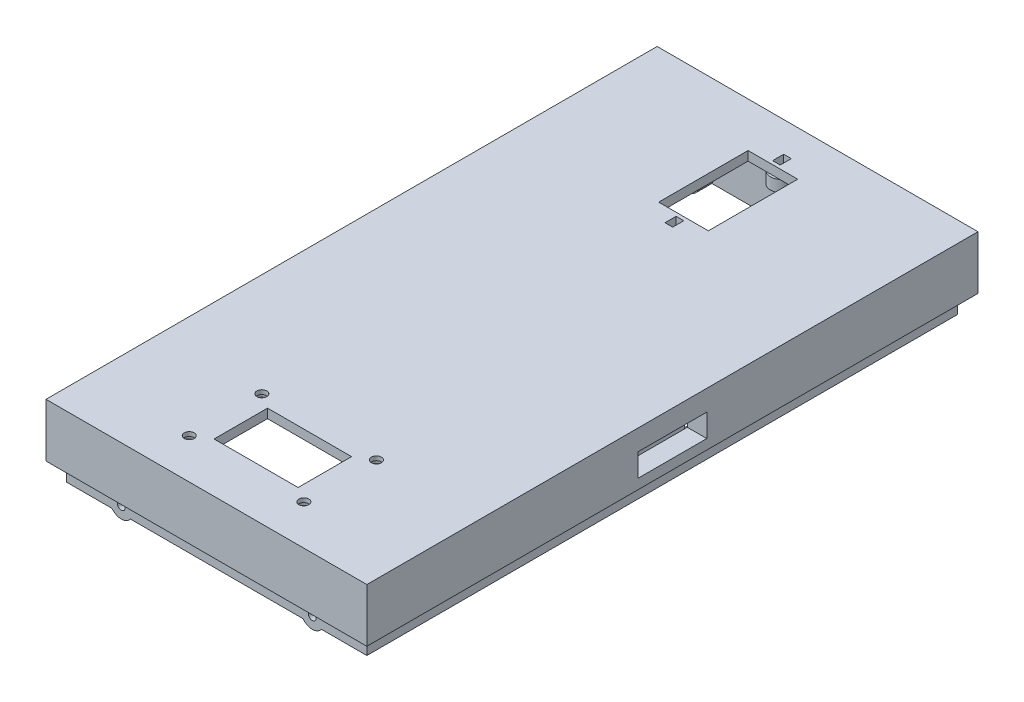
SolidWorks part; units mm, degrees
ref_plane "Front Plane" through (0, 0, 0) normal (0, 0, 1) x (1, 0, 0)
ref_plane "Top Plane" through (0, 0, 0) normal (0, 1, 0) x (1, 0, 0)
ref_plane "Right Plane" through (0, 0, 0) normal (1, 0, 0) x (0, 0, -1)
sketch "Sketch1" plane through (0, 0, 0) normal (0, 0, 1) x (1, 0, 0)
  line L1 (-42, 36) -> (42, 36)
  line L2 (-42, 36) -> (-42, 50)
  line L3 (-42, 50) -> (42, 50)
  line L4 (42, 36) -> (42, 50)
extrude "Boss-Extrude1" add sketch "Sketch1" along normal blind 160 from offset 80 offset against normal yes
sketch "Sketch2" plane through (0, 0, 0) normal (0, 0, 1) x (1, 0, 0)
  line L1 (-39.3, 31.2) -> (39.3, 31.2)
  line L2 (-39.3, 31.2) -> (-39.3, 36.5)
  line L3 (-39.3, 36.5) -> (39.3, 36.5)
  line L4 (39.3, 31.2) -> (39.3, 36.5)
extrude "Boss-Extrude2" add sketch "Sketch2" along normal blind 154.6 from offset 77.3 offset against normal yes
sketch "Sketch3" plane through (0, 0, 0) normal (0, 0, 1) x (1, 0, 0)
  line L1 (-36.9, 30.2) -> (36.9, 30.2)
  line L2 (-36.9, 30.2) -> (-36.9, 47.6)
  line L3 (-36.9, 47.6) -> (36.9, 47.6)
  line L4 (36.9, 30.2) -> (36.9, 47.6)
extrude "Boss-Extrude3" add sketch "Sketch3" along normal blind 149.8 from offset 74.9 separate body offset against normal yes
combine bodies "Combine1" operation type subtract main body 102 bodies to subtract 103
sketch "Sketch4" plane through (0, 0, 0) normal (0, 0, 1) x (1, 0, 0)
  circle A0 centre (-25, 33) radius 3
extrude "Boss-Extrude4" add sketch "Sketch4" along normal blind 6.3 from offset 77.3 offset against normal yes
sketch "Sketch5" plane through (0, 0, 0) normal (0, 0, 1) x (1, 0, 0)
  circle A0 centre (-25, 33) radius 1
extrude "Boss-Extrude5" add sketch "Sketch5" along normal blind 8 from offset 78 separate body offset against normal yes
combine bodies "Combine2" operation type subtract main body 105 bodies to subtract 106
sketch "Sketch6" plane through (0, 0, 0) normal (0, 0, 1) x (1, 0, 0)
  circle A0 centre (25, 33) radius 3
extrude "Boss-Extrude6" add sketch "Sketch6" along normal blind 6.3 from offset 77.3 offset against normal yes
sketch "Sketch7" plane through (0, 0, 0) normal (0, 0, 1) x (1, 0, 0)
  circle A0 centre (25, 33) radius 1
extrude "Boss-Extrude7" add sketch "Sketch7" along normal blind 8 from offset 78 separate body offset against normal yes
combine bodies "Combine3" operation type subtract main body 108 bodies to subtract 109
sketch "Sketch8" plane through (0, 0, 0) normal (0, 0, 1) x (1, 0, 0)
  circle A0 centre (-25, 33) radius 3
extrude "Boss-Extrude8" add sketch "Sketch8" along normal blind 6.3 from offset 71
sketch "Sketch9" plane through (0, 0, 0) normal (0, 0, 1) x (1, 0, 0)
  circle A0 centre (-25, 33) radius 1
extrude "Boss-Extrude9" add sketch "Sketch9" along normal blind 8 from offset 70 separate body
combine bodies "Combine4" operation type subtract main body 111 bodies to subtract 112
sketch "Sketch10" plane through (0, 0, 0) normal (0, 0, 1) x (1, 0, 0)
  circle A0 centre (25, 33) radius 3
extrude "Boss-Extrude10" add sketch "Sketch10" along normal blind 6.3 from offset 71
sketch "Sketch11" plane through (0, 0, 0) normal (0, 0, 1) x (1, 0, 0)
  circle A0 centre (25, 33) radius 1
extrude "Boss-Extrude11" add sketch "Sketch11" along normal blind 8 from offset 70 separate body
combine bodies "Combine5" operation type subtract main body 114 bodies to subtract 115
sketch "Sketch12" plane through (0, 0, 0) normal (0, 0, 1) x (1, 0, 0)
  line L1 (-11, 46.6) -> (11, 46.6)
  line L2 (-11, 46.6) -> (-11, 51)
  line L3 (-11, 51) -> (11, 51)
  line L4 (11, 46.6) -> (11, 51)
extrude "Boss-Extrude12" add sketch "Sketch12" along normal blind 14 from offset 53 separate body
combine bodies "Combine6" operation type subtract main body 116 bodies to subtract 117
sketch "Sketch13" plane through (0, 0, 0) normal (0, 1, 0) x (1, 0, 0)
  circle A0 centre (-15, -50.5) radius 1.3
extrude "Boss-Extrude13" add sketch "Sketch13" along normal blind 4.4 from offset 46.6 separate body
combine bodies "Combine7" operation type subtract main body 118 bodies to subtract 119
sketch "Sketch14" plane through (0, 0, 0) normal (0, 1, 0) x (1, 0, 0)
  circle A0 centre (-15, -50.5) radius 2.3
extrude "Boss-Extrude14" add sketch "Sketch14" along normal blind 1.8 from offset 47.1 separate body
combine bodies "Combine8" operation type subtract main body 120 bodies to subtract 121
sketch "Sketch15" plane through (0, 0, 0) normal (0, 1, 0) x (1, 0, 0)
  circle A0 centre (-15, -69.5) radius 1.3
extrude "Boss-Extrude15" add sketch "Sketch15" along normal blind 4.4 from offset 46.6 separate body
combine bodies "Combine9" operation type subtract main body 122 bodies to subtract 123
sketch "Sketch16" plane through (0, 0, 0) normal (0, 1, 0) x (1, 0, 0)
  circle A0 centre (-15, -69.5) radius 2.3
extrude "Boss-Extrude16" add sketch "Sketch16" along normal blind 1.8 from offset 47.1 separate body
combine bodies "Combine10" operation type subtract main body 124 bodies to subtract 125
sketch "Sketch17" plane through (0, 0, 0) normal (0, 1, 0) x (1, 0, 0)
  circle A0 centre (15, -50.5) radius 1.3
extrude "Boss-Extrude17" add sketch "Sketch17" along normal blind 4.4 from offset 46.6 separate body
combine bodies "Combine11" operation type subtract main body 126 bodies to subtract 127
sketch "Sketch18" plane through (0, 0, 0) normal (0, 1, 0) x (1, 0, 0)
  circle A0 centre (15, -50.5) radius 2.3
extrude "Boss-Extrude18" add sketch "Sketch18" along normal blind 1.8 from offset 47.1 separate body
combine bodies "Combine12" operation type subtract main body 128 bodies to subtract 129
sketch "Sketch19" plane through (0, 0, 0) normal (0, 1, 0) x (1, 0, 0)
  circle A0 centre (15, -69.5) radius 1.3
extrude "Boss-Extrude19" add sketch "Sketch19" along normal blind 4.4 from offset 46.6 separate body
combine bodies "Combine13" operation type subtract main body 130 bodies to subtract 131
sketch "Sketch20" plane through (0, 0, 0) normal (0, 1, 0) x (1, 0, 0)
  circle A0 centre (15, -69.5) radius 2.3
extrude "Boss-Extrude20" add sketch "Sketch20" along normal blind 1.8 from offset 47.1 separate body
combine bodies "Combine14" operation type subtract main body 132 bodies to subtract 133
sketch "Sketch21" plane through (0, 0, 0) normal (0, 0, 1) x (1, 0, 0)
  line L1 (-6.5, 46.6) -> (6.5, 46.6)
  line L2 (-6.5, 46.6) -> (-6.5, 51)
  line L3 (-6.5, 51) -> (6.5, 51)
  line L4 (6.5, 46.6) -> (6.5, 51)
extrude "Boss-Extrude21" add sketch "Sketch21" along normal blind 23.4 from offset 68.3 separate body offset against normal yes
combine bodies "Combine15" operation type subtract main body 134 bodies to subtract 135
sketch "Sketch22" plane through (0, 0, 0) normal (0, 1, 0) x (1, 0, 0)
  circle A0 centre (0, 70.675) radius 3
extrude "Boss-Extrude22" add sketch "Sketch22" along normal blind 3 from offset 44.6
sketch "Sketch23" plane through (0, 0, 0) normal (0, 0, 1) x (1, 0, 0)
  line L1 (-1, 43.6) -> (1, 43.6)
  line L2 (-1, 43.6) -> (-1, 51)
  line L3 (-1, 51) -> (1, 51)
  line L4 (1, 43.6) -> (1, 51)
extrude "Boss-Extrude23" add sketch "Sketch23" along normal blind 2.9 from offset 72.125 separate body offset against normal yes
combine bodies "Combine16" operation type subtract main body 137 bodies to subtract 138
sketch "Sketch24" plane through (0, 0, 0) normal (0, 1, 0) x (1, 0, 0)
  circle A0 centre (0, 42.525) radius 3
extrude "Boss-Extrude24" add sketch "Sketch24" along normal blind 3 from offset 44.6
sketch "Sketch25" plane through (0, 0, 0) normal (0, 0, 1) x (1, 0, 0)
  line L1 (-1, 43.6) -> (1, 43.6)
  line L2 (-1, 43.6) -> (-1, 51)
  line L3 (-1, 51) -> (1, 51)
  line L4 (1, 43.6) -> (1, 51)
extrude "Boss-Extrude25" add sketch "Sketch25" along normal blind 2.9 from offset 43.975 separate body offset against normal yes
combine bodies "Combine17" operation type subtract main body 140 bodies to subtract 141
sketch "Sketch26" plane through (0, 0, 0) normal (0, 0, 1) x (1, 0, 0)
  line L1 (-43, 38.6) -> (-36, 38.6)
  line L2 (-43, 38.6) -> (-43, 44.6)
  line L3 (-43, 44.6) -> (-36, 44.6)
  line L4 (-36, 38.6) -> (-36, 44.6)
extrude "Boss-Extrude26" add sketch "Sketch26" along normal blind 18 from offset 9 separate body offset against normal yes
combine bodies "Combine18" operation type subtract main body 142 bodies to subtract 143
sketch "Sketch27" plane through (0, 0, 0) normal (0, 0, 1) x (1, 0, 0)
  line L1 (-36.9, 34.4) -> (-33.6, 34.4)
  line L2 (-36.9, 34.4) -> (-36.9, 35.6)
  line L3 (-36.9, 35.6) -> (-33.6, 35.6)
  line L4 (-33.6, 34.4) -> (-33.6, 35.6)
extrude "Boss-Extrude27" add sketch "Sketch27" along normal blind 27 from offset 13.5 offset against normal yes
sketch "Sketch28" plane through (0, 0, 0) normal (0, 0, 1) x (1, 0, 0)
  line L1 (-34.2, 34.4) -> (-33, 34.4)
  line L2 (-34.2, 34.4) -> (-34.2, 38)
  line L3 (-34.2, 38) -> (-33, 38)
  line L4 (-33, 34.4) -> (-33, 38)
extrude "Boss-Extrude28" add sketch "Sketch28" along normal blind 22 from offset 11 offset against normal yes
sketch "Sketch29" plane through (0, 0, 0) normal (0, 0, 1) x (1, 0, 0)
  line L1 (36, 38.6) -> (43, 38.6)
  line L2 (36, 38.6) -> (36, 44.6)
  line L3 (36, 44.6) -> (43, 44.6)
  line L4 (43, 38.6) -> (43, 44.6)
extrude "Boss-Extrude29" add sketch "Sketch29" along normal blind 18 from offset 9 separate body offset against normal yes
combine bodies "Combine19" operation type subtract main body 146 bodies to subtract 147
sketch "Sketch30" plane through (0, 0, 0) normal (0, 0, 1) x (1, 0, 0)
  line L1 (33.6, 34.4) -> (36.9, 34.4)
  line L2 (33.6, 34.4) -> (33.6, 35.6)
  line L3 (33.6, 35.6) -> (36.9, 35.6)
  line L4 (36.9, 34.4) -> (36.9, 35.6)
extrude "Boss-Extrude30" add sketch "Sketch30" along normal blind 27 from offset 13.5 offset against normal yes
sketch "Sketch31" plane through (0, 0, 0) normal (0, 0, 1) x (1, 0, 0)
  line L1 (33, 34.4) -> (34.2, 34.4)
  line L2 (33, 34.4) -> (33, 38)
  line L3 (33, 38) -> (34.2, 38)
  line L4 (34.2, 34.4) -> (34.2, 38)
extrude "Boss-Extrude31" add sketch "Sketch31" along normal blind 22 from offset 11 offset against normal yes
sketch "Sketch32" plane through (0, 0, 0) normal (0, 0, 1) x (1, 0, 0)
  line L1 (-9.8, 45.1) -> (-8.6, 45.1)
  line L2 (-9.8, 45.1) -> (-9.8, 47.6)
  line L3 (-9.8, 47.6) -> (-8.6, 47.6)
  line L4 (-8.6, 45.1) -> (-8.6, 47.6)
extrude "Boss-Extrude32" add sketch "Sketch32" along normal blind 22.4 from offset 3.6
sketch "Sketch33" plane through (0, 0, 0) normal (0, 0, 1) x (1, 0, 0)
  line L1 (8.6, 45.1) -> (9.8, 45.1)
  line L2 (8.6, 45.1) -> (8.6, 47.6)
  line L3 (8.6, 47.6) -> (9.8, 47.6)
  line L4 (9.8, 45.1) -> (9.8, 47.6)
extrude "Boss-Extrude33" add sketch "Sketch33" along normal blind 22.4 from offset 3.6
sketch "Sketch34" plane through (0, 0, 0) normal (0, 0, 1) x (1, 0, 0)
  line L1 (-9.8, 45.1) -> (9.8, 45.1)
  line L2 (-9.8, 45.1) -> (-9.8, 47.6)
  line L3 (-9.8, 47.6) -> (9.8, 47.6)
  line L4 (9.8, 45.1) -> (9.8, 47.6)
extrude "Boss-Extrude34" add sketch "Sketch34" along normal blind 1.2 from offset 2.4
sketch "Sketch35" plane through (0, 0, 0) normal (0, 0, 1) x (1, 0, 0)
  line L1 (-9.8, 45.1) -> (9.8, 45.1)
  line L2 (-9.8, 45.1) -> (-9.8, 47.6)
  line L3 (-9.8, 47.6) -> (9.8, 47.6)
  line L4 (9.8, 45.1) -> (9.8, 47.6)
extrude "Boss-Extrude35" add sketch "Sketch35" along normal blind 1.2 from offset 26
sketch "Sketch36" plane through (0, 0, 0) normal (0, 0, 1) x (1, 0, 0)
  line L1 (14.9, 45.1) -> (16.1, 45.1)
  line L2 (14.9, 45.1) -> (14.9, 47.6)
  line L3 (14.9, 47.6) -> (16.1, 47.6)
  line L4 (16.1, 45.1) -> (16.1, 47.6)
extrude "Boss-Extrude36" add sketch "Sketch36" along normal blind 30.5 from offset 16.5
sketch "Sketch37" plane through (0, 0, 0) normal (0, 0, 1) x (1, 0, 0)
  line L1 (14.9, 45.1) -> (36.9, 45.1)
  line L2 (14.9, 45.1) -> (14.9, 47.6)
  line L3 (14.9, 47.6) -> (36.9, 47.6)
  line L4 (36.9, 45.1) -> (36.9, 47.6)
extrude "Boss-Extrude37" add sketch "Sketch37" along normal blind 1.2 from offset 15.3
sketch "Sketch38" plane through (0, 0, 0) normal (0, 0, 1) x (1, 0, 0)
  line L1 (-26.4, 45.1) -> (-25.2, 45.1)
  line L2 (-26.4, 45.1) -> (-26.4, 47.6)
  line L3 (-26.4, 47.6) -> (-25.2, 47.6)
  line L4 (-25.2, 45.1) -> (-25.2, 47.6)
extrude "Boss-Extrude38" add sketch "Sketch38" along normal blind 36 from offset 37.5 offset against normal yes
sketch "Sketch39" plane through (0, 0, 0) normal (0, 0, 1) x (1, 0, 0)
  line L1 (25.2, 45.1) -> (26.4, 45.1)
  line L2 (25.2, 45.1) -> (25.2, 47.6)
  line L3 (25.2, 47.6) -> (26.4, 47.6)
  line L4 (26.4, 45.1) -> (26.4, 47.6)
extrude "Boss-Extrude39" add sketch "Sketch39" along normal blind 36 from offset 37.5 offset against normal yes
sketch "Sketch40" plane through (0, 0, 0) normal (0, 0, 1) x (1, 0, 0)
  line L1 (-26.4, 45.1) -> (26.4, 45.1)
  line L2 (-26.4, 45.1) -> (-26.4, 47.6)
  line L3 (-26.4, 47.6) -> (26.4, 47.6)
  line L4 (26.4, 45.1) -> (26.4, 47.6)
extrude "Boss-Extrude40" add sketch "Sketch40" along normal blind 1.2 from offset 38.7 offset against normal yes
sketch "Sketch41" plane through (0, 0, 0) normal (0, 0, 1) x (1, 0, 0)
  line L1 (-26.4, 45.1) -> (26.4, 45.1)
  line L2 (-26.4, 45.1) -> (-26.4, 47.6)
  line L3 (-26.4, 47.6) -> (26.4, 47.6)
  line L4 (26.4, 45.1) -> (26.4, 47.6)
extrude "Boss-Extrude41" add sketch "Sketch41" along normal blind 1.2 from offset 1.5 offset against normal yes
